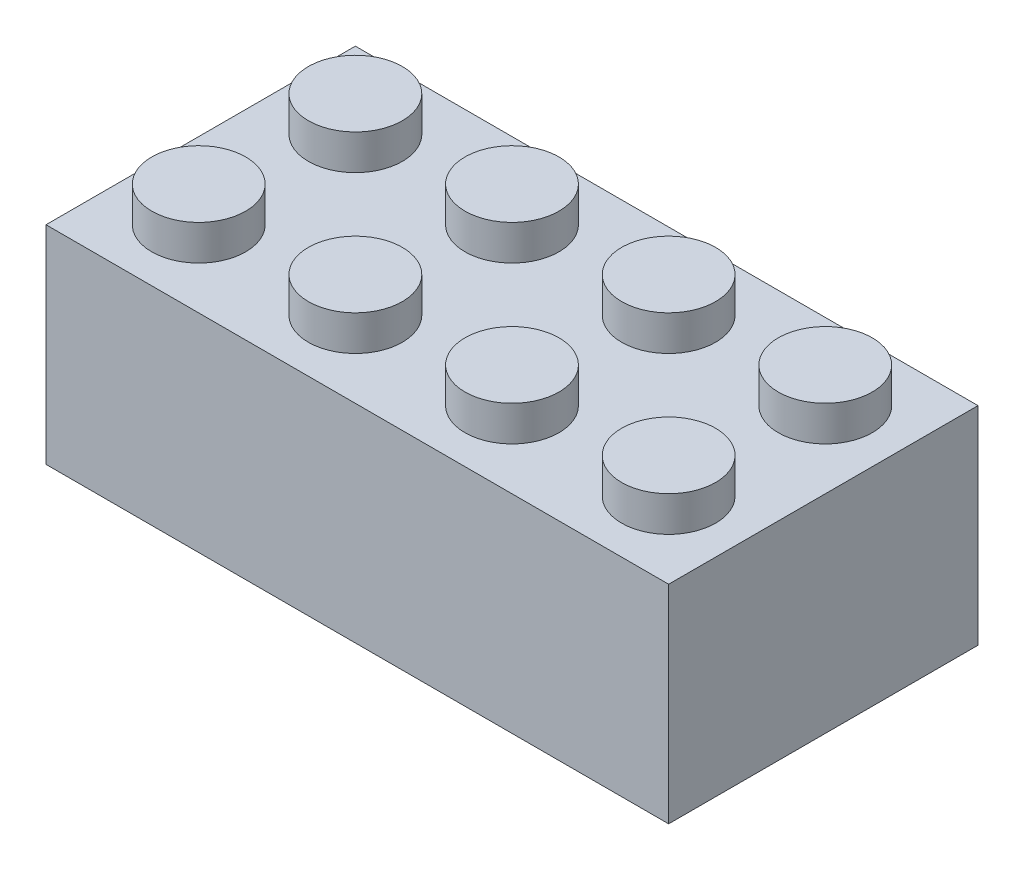
SolidWorks part; units mm, degrees
material "ABS"
ref_plane "Front Plane" through (0, 0, 0) normal (0, 0, 1) x (1, 0, 0)
ref_plane "Top Plane" through (0, 0, 0) normal (0, 1, 0) x (1, 0, 0)
ref_plane "Right Plane" through (0, 0, 0) normal (1, 0, 0) x (0, 0, -1)
sketch "Sketch1" plane through (0, 0, 0) normal (0, 1, 0) x (1, 0, 0)
  line L0 (483.8014, 243.2314) -> (307.1468, 155.4596) construction
  line L2 (-500.5732, 155.4596) -> (-500.5732, -245.8604)
  line L3 (-500.5732, -245.8604) -> (307.1468, -245.8604)
  line L4 (307.1468, 155.4596) -> (307.1468, -245.8604)
  line L5 (-500.5732, 155.4596) -> (307.1468, 155.4596)
  line L6 (-500.5732, -245.8604) -> (-461.9702, -226.6803) construction
  line L11 (-416.7532, 124.9796) -> (-416.7532, 119.8996)
  line L12 (-470.0932, 124.9796) -> (-416.7532, 124.9796)
  line L13 (276.6668, -215.3804) -> (307.1468, -245.8604) construction
  line L14 (-470.0932, 124.9796) -> (-470.0932, 71.6396)
  line L15 (-470.0932, -215.3804) -> (276.6668, -215.3804)
  line L16 (276.6668, 124.9796) -> (276.6668, 71.6396)
  line L17 (-526.0793, -45.2004) -> (393.5365, -45.2004) construction
  line L18 (-96.7132, -309.2679) -> (-96.7132, 236.2117) construction
  line L19 (-416.7532, 119.8996) -> (-386.2732, 119.8996)
  line L20 (-386.2732, 119.8996) -> (-386.2732, 124.9796)
  line L21 (-206.4186, 124.9796) -> (-206.4186, 119.8996)
  line L22 (-206.4186, 119.8996) -> (-175.9512, 119.8996)
  line L23 (-175.9512, 119.8996) -> (-175.9512, 124.9796)
  line L24 (-470.0932, 71.6396) -> (-465.0132, 71.6396)
  line L25 (-465.0132, 71.6396) -> (-465.0132, 41.1596)
  line L26 (-465.0132, 41.1596) -> (-470.0932, 41.1596)
  line L27 (-401.5132, 119.8996) -> (-401.5132, -45.2004) construction
  line L28 (-465.0132, 56.3996) -> (-352.6242, 56.3996) construction
  line L29 (-299.9132, -45.2004) -> (-299.9132, 124.9796) construction
  line L30 (-386.2732, 124.9796) -> (-206.4186, 124.9796)
  line L31 (-175.9512, 124.9796) -> (-17.4752, 124.9796)
  line L32 (-470.0932, 41.1596) -> (-470.0932, -131.5604)
  line L33 (-470.0932, -162.0404) -> (-465.0132, -162.0404)
  line L34 (-465.0132, -162.0404) -> (-465.0132, -131.5604)
  line L35 (-465.0132, -131.5604) -> (-470.0932, -131.5604)
  line L36 (-470.0932, -162.0404) -> (-470.0932, -215.3804)
  line L37 (-17.4752, 119.8996) -> (-17.4752, 124.9796)
  line L38 (12.9923, 119.8996) -> (-17.4752, 119.8996)
  line L39 (12.9923, 124.9796) -> (12.9923, 119.8996)
  line L40 (192.8468, 119.8996) -> (192.8468, 124.9796)
  line L41 (223.3268, 119.8996) -> (192.8468, 119.8996)
  line L42 (223.3268, 124.9796) -> (223.3268, 119.8996)
  line L43 (12.9923, 124.9796) -> (192.8468, 124.9796)
  line L44 (223.3268, 124.9796) -> (276.6668, 124.9796)
  line L45 (276.6668, -162.0404) -> (271.5868, -162.0404)
  line L46 (271.5868, -162.0404) -> (271.5868, -131.5604)
  line L47 (271.5868, -131.5604) -> (276.6668, -131.5604)
  line L48 (276.6668, 71.6396) -> (271.5868, 71.6396)
  line L49 (271.5868, 41.1596) -> (276.6668, 41.1596)
  line L50 (271.5868, 71.6396) -> (271.5868, 41.1596)
  line L51 (276.6668, -162.0404) -> (276.6668, -215.3804)
  line L52 (276.6668, 41.1596) -> (276.6668, -131.5604)
  point P30 (0, 0)
  point P33 (0, 0)
  dimension "D1" = 807.72
  dimension "D2" = 401.32
  dimension "D3" = 30.48
  dimension "D4" = 30.48
  dimension "D5" = 30.48
  dimension "D6" = 30.48
  dimension "D7" = 5.08
  dimension "D8" = 30.48
  dimension "D9" = 5.08
  dimension "D10" = 101.6
  dimension "D11" = 30.48
  dimension "D12" = 203.2
  dimension "D13" = 101.6
extrude "Boss-Extrude1" add sketch "Sketch1" along normal blind 25.4 contours L52 L49 L50 L48 L16 L44 L42 L41 L40 L43 L39 L38 L37 L31 L23 L22 L21 L30 L20 L19 L11 L12 L14 L24 L25 L26 L32 L35 L34 L33 L36 L15 L51 L45 L46 L47 | L5 L2 L3 L4 L49 L52 L47 L46 L45 L51 L15 L36 L33 L34 L35 L32 L26 L25 L24 L14 L12 L11 L19 L20 L30 L21 L22 L23 L31 L37 L38 L39 L43 L40 L41 L42 L44 L16 L48 L50 region at (-96.7132, 0, -146.4404) region at (-96.7132, 0, 45.6108)
extrude "Boss-Extrude2" add sketch "Sketch1<3>" against normal blind 243.84
sketch "Sketch1<3>" plane through (0, 0, 0) normal (0, 1, 0) x (1, 0, 0) same geometry as "Sketch1"
sketch "Sketch2" plane through (0, 25.4, 0) normal (0, 1, 0) x (1, 0, 0)
  line L0 (-96.7132, -245.8604) -> (-96.7132, 402.1611) construction
  line L1 (-500.5732, -245.8604) -> (307.1468, -245.8604) construction
  line L2 (-500.5732, -45.2004) -> (368.4287, -45.2004) construction
  line L3 (-500.5732, 155.4596) -> (-500.5732, -245.8604) construction
  line L4 (-540.4656, 56.3996) -> (345.4748, 56.3996) construction
  line L5 (-305.0404, 155.4596) -> (-305.0404, -245.8604) construction
  line L6 (-500.5732, 155.4596) -> (307.1468, 155.4596) construction
  circle A0 centre (-401.5132, 56.3996) radius 60.96
  circle A1 centre (-198.3132, 56.3996) radius 60.96
  circle A8 centre (-198.3132, -146.8004) radius 60.96
  circle A9 centre (-401.5132, -146.8004) radius 60.96
  circle A10 centre (208.0868, -146.8004) radius 60.96
  circle A11 centre (4.8868, -146.8004) radius 60.96
  circle A12 centre (4.8868, 56.3996) radius 60.96
  circle A13 centre (208.0868, 56.3996) radius 60.96
  circle A14 centre (-401.5132, 56.3996) radius 30.48
  circle A15 centre (-198.3132, 56.3996) radius 30.48
  circle A18 centre (-198.3132, -146.8004) radius 30.48
  circle A19 centre (-401.5132, -146.8004) radius 30.48
  circle A20 centre (4.8868, -146.8004) radius 30.48
  circle A21 centre (4.8868, 56.3996) radius 30.48
  circle A22 centre (208.0868, 56.3996) radius 30.48
  circle A23 centre (208.0868, -146.8004) radius 30.48
  dimension "D1" = 121.92
  dimension "D5" = 30.48
  dimension "D2" = 304.8
  dimension "D3" = 101.6
  dimension "D4" = 101.6
extrude "Boss-Extrude3" add sketch "Sketch2" along normal blind 45.72 contours A22 | A13 A22 | A10 A23 | A23 | A11 A20 | A20 | A1 A15 | A15 | A9 A19 | A19 | A0 A14 | A14 | A12 A21 | A21 | A8 A18 | A18 region at (-460.749, 25.4, -56.3996) region at (-257.549, 25.4, -56.3996) region at (-257.549, 25.4, 146.8004) region at (-460.749, 25.4, 146.8004) region at (148.851, 25.4, 146.8004) region at (-54.349, 25.4, 146.8004) region at (-54.349, 25.4, -56.3996) region at (148.851, 25.4, -56.3996) region at (-401.5132, 25.4, -56.3996) region at (-198.3132, 25.4, -56.3996) region at (-401.5132, 25.4, 146.8004) region at (4.8868, 25.4, 146.8004) region at (4.8868, 25.4, -56.3996) region at (208.0868, 25.4, -56.3996) region at (208.0868, 25.4, 146.8004)
sketch "Sketch3" plane through (0, 0, 0) normal (0, -1, 0) x (1, 0, 0)
  line L0 (-470.0932, 45.2004) -> (322.0142, 45.2004) construction
  line L1 (-470.0932, -41.1596) -> (-470.0932, 131.5604) construction
  line L2 (-96.7132, -124.9796) -> (-96.7132, 384.969) construction
  line L3 (-17.4752, -124.9796) -> (-175.9512, -124.9796) construction
  line L4 (-110.6832, 126.5597) -> (-110.6832, 215.3804)
  line L5 (-470.0932, 215.3804) -> (276.6668, 215.3804) construction
  line L6 (-110.6832, 215.3804) -> (-82.7432, 215.3804)
  line L7 (-82.7432, 215.3804) -> (-82.7432, 126.5597)
  line L8 (-82.7432, -124.9796) -> (-82.7432, -36.159)
  line L9 (-110.6832, -124.9796) -> (-82.7432, -124.9796)
  line L10 (-110.6832, -36.159) -> (-110.6832, -124.9796)
  circle A0 centre (-299.9132, 45.2004) radius 82.55
  circle A1 centre (-96.7132, 45.2004) radius 82.55
  circle A2 centre (106.4868, 45.2004) radius 82.55
  circle A3 centre (-299.9132, 45.2004) radius 52.07
  circle A4 centre (-96.7132, 45.2004) radius 52.07
  circle A5 centre (106.4868, 45.2004) radius 52.07
  line M12 (-175.9512, -124.9796) -> (-17.4752, -124.9796)
  line M30 (276.6668, 215.3804) -> (-470.0932, 215.3804)
  dimension "D1" = 165.1
  dimension "D2" = 30.48
  dimension "D3" = 203.2
  dimension "D4" = 27.94
extrude "Boss-Extrude4" add sketch "Sketch3" along normal up to surface (243.84 mm away) contours A2 A5 | A1 A4 | A0 A3 region at (-96.7132, 0, 125.4155) region at (-380.1283, 0, 45.2004) region at (26.2717, 0, 45.2004) up to face at (-96.7132, -243.84, -29.3063)
extrude "Boss-Extrude5" add sketch "Sketch3<4>" along normal blind 167.64 contours A1 L7 L4 M30 | A1 L10 L8 M12 region at (-96.7132, 0, 171.3668) region at (-96.7132, 0, -80.966)
sketch "Sketch3<4>" plane through (0, 0, 0) normal (0, -1, 0) x (1, 0, 0) same geometry as "Sketch3"
extrude "Cut-Extrude3" cut sketch "Sketch2<6>" against normal blind 25.4 and the other way blind 25.4 contours A14 | A15 | A18 | A23 | A22 | A19 | A20 region at (-401.5132, 25.4, -56.3996) region at (-198.3132, 25.4, -56.3996) region at (-198.3132, 25.4, 146.8004) region at (208.0868, 25.4, -56.3996) region at (208.0868, 25.4, 146.8004)
sketch "Sketch2<6>" plane through (0, 25.4, 0) normal (0, 1, 0) x (1, 0, 0) same geometry as "Sketch2"
